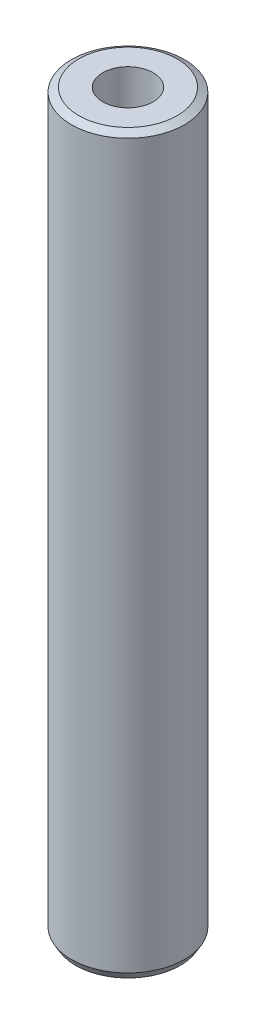
SolidWorks part; units mm, degrees
ref_plane "Front Plane" through (0, 0, 0) normal (0, 0, 1) x (1, 0, 0)
ref_plane "Top Plane" through (0, 0, 0) normal (0, 1, 0) x (1, 0, 0)
ref_plane "Right Plane" through (0, 0, 0) normal (1, 0, 0) x (0, 0, -1)
sketch "Sketch1" plane through (0, 0, 0) normal (0, 1, 0) x (1, 0, 0)
  circle A0 centre (0, 0) radius 40
  dimension "SHAFT_OD" = 80
extrude "Boss-Extrude1" add sketch "Sketch1" along normal blind 519.7709
sketch "Sketch2" plane through (0, 0, 0) normal (0, 1, 0) x (1, 0, 0)
  circle A0 centre (0, 0) radius 17.8575
  dimension "BORE_D" = 35.7151
extrude "Cut-Extrude1" cut sketch "Sketch2" along normal through all
chamfer "Chamfer1" distance 2.9889 angle 60 2 edges at (0, 519.7709, 40) (0, 0, 40) first distance on face at (0, 519.7709, 40) first distance on face at (0, 0, 17.8575)
